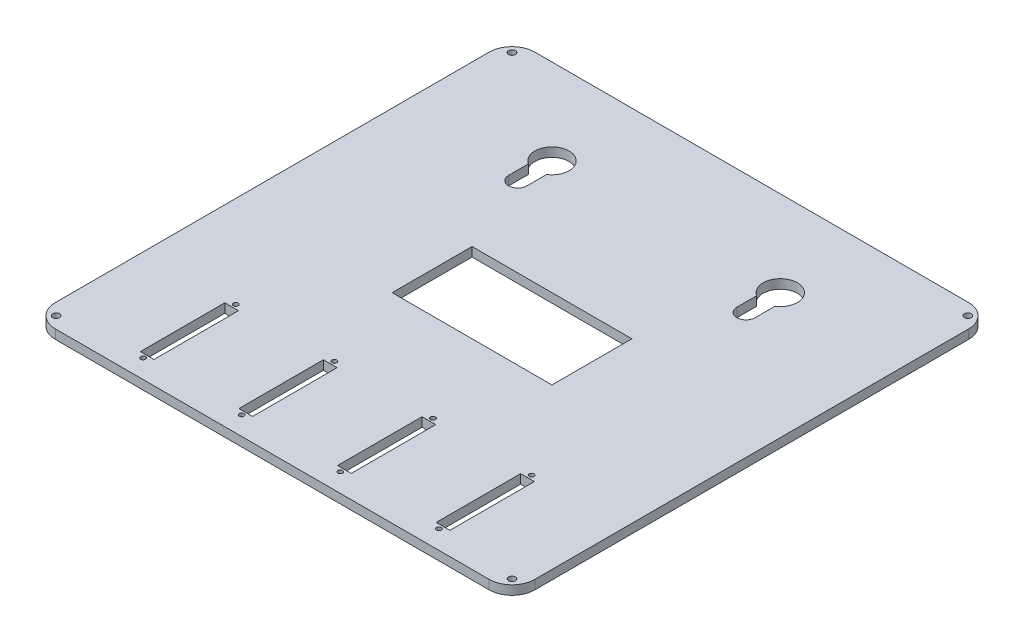
SolidWorks part; units mm, degrees
ref_plane "Front Plane" through (0, 0, 0) normal (0, 0, 1) x (1, 0, 0)
ref_plane "Top Plane" through (0, 0, 0) normal (0, 1, 0) x (1, 0, 0)
ref_plane "Right Plane" through (0, 0, 0) normal (1, 0, 0) x (0, 0, -1)
sketch "Sketch1" plane through (0, 0, 0) normal (0, 1, 0) x (1, 0, 0)
  line L0 (-101, -101) -> (-101, 101)
  line L5 (-105, -105) -> (105, -105)
  line L6 (-105, -105) -> (-105, 105)
  line L7 (-105, 105) -> (105, 105)
  line L8 (105, -105) -> (105, 105)
  line L9 (-101, 101) -> (101, 101)
  line L10 (101, -101) -> (101, 101)
  line L11 (-101, -101) -> (101, -101)
  line L12 (-101, 101) -> (-99.8333, 99.8333) construction
  line L13 (-55, 0) -> (55, 0) construction
  line L14 (-101, -101) -> (-99.8333, -99.8333) construction
  line L15 (0, -55) -> (0, 55) construction
  line L16 (101, -101) -> (99.8333, -99.8333) construction
  line L17 (101, 101) -> (99.8333, 99.8333) construction
  circle A1 centre (-99.8333, 99.8333) radius 1.5
  circle A2 centre (-99.8333, -99.8333) radius 1.5
  circle A3 centre (99.8333, -99.8333) radius 1.5
  circle A4 centre (99.8333, 99.8333) radius 1.5
  point P0 (0, 0)
  point P6 (-105, 0)
  point P7 (0, 105)
  dimension "D3" = 4
  dimension "D4" = 3
  dimension "D1" = 210
  dimension "D2" = 210
  dimension "D5" = 1.65
  dimension "D6" = 45
extrude "MainExtrude" add sketch "Sketch1" along normal mid plane 4 contours L6 L5 L8 L7
extrude "ScrewHoles" cut sketch "Sketch1<6>" along normal mid plane 4 contours A1 | A2 | A3 | A4
sketch "Sketch1<6>" plane through (0, 0, 0) normal (0, 1, 0) x (1, 0, 0) same geometry as "Sketch1"
fillet "RoundedCorners" radius 10 4 edges at (-105, 0, -105) (-105, 0, 105) (105, 0, -105) (105, 0, 105)
sketch "Sketch2" plane through (0, 2, 0) normal (0, 1, 0) x (1, 0, 0)
  line L0 (-50, 67.5) -> (-50, 52.5) construction
  line L1 (-67.8, -58) -> (-61.8, -58)
  line L2 (-67.8, -58) -> (-67.8, -95)
  line L3 (-67.8, -95) -> (-61.8, -95)
  line L4 (-61.8, -58) -> (-61.8, -95)
  line L5 (-24.6, -58) -> (-18.6, -58)
  line L6 (-24.6, -58) -> (-24.6, -95)
  line L7 (-24.6, -95) -> (-18.6, -95)
  line L8 (-18.6, -58) -> (-18.6, -95)
  line L9 (18.6, -58) -> (24.6, -58)
  line L10 (18.6, -58) -> (18.6, -95)
  line L11 (18.6, -95) -> (24.6, -95)
  line L12 (24.6, -58) -> (24.6, -95)
  line L13 (61.8, -58) -> (67.8, -58)
  line L14 (61.8, -58) -> (61.8, -95)
  line L15 (61.8, -95) -> (67.8, -95)
  line L16 (67.8, -58) -> (67.8, -95)
  line L17 (-95, -105) -> (95, -105) construction
  line L19 (-67.8, -58) -> (-105, -58) construction
  line L20 (-105, -95) -> (-105, 95) construction
  line L21 (-61.8, -58) -> (-24.6, -58) construction
  line L22 (-18.6, -58) -> (18.6, -58) construction
  line L23 (24.6, -58) -> (61.8, -58) construction
  line L25 (-105, 60) -> (-50, 60) construction
  line L26 (-95, 105) -> (95, 105) construction
  line L30 (-54, 52.5) -> (-54, 61.1557)
  line L31 (-46, 52.5) -> (-46, 61.1557)
  line L32 (0, -3.3) -> (0, 3.3) construction
  line L33 (46, 52.5) -> (46, 61.1557)
  line L34 (54, 52.5) -> (54, 61.1557)
  line L36 (35, -17.5) -> (-35, -17.5)
  line L37 (35, -17.5) -> (35, 17.5)
  line L38 (35, 17.5) -> (-35, 17.5)
  line L39 (-35, -17.5) -> (-35, 17.5)
  arc A0 (-54, 52.5) -> (-46, 52.5) centre (-50, 52.5) ccw
  arc A4 (-46, 61.1557) -> (-54, 61.1557) centre (-50, 67.5) ccw
  arc A5 (54, 52.5) -> (46, 52.5) centre (50, 52.5) cw
  arc A6 (46, 61.1557) -> (54, 61.1557) centre (50, 67.5) cw
  circle A7 centre (-64.8, -96.8) radius 1.05
  circle A8 centre (-64.8, -56.2) radius 1.05
  circle A9 centre (-21.6, -56.2) radius 1.05
  circle A10 centre (-21.6, -96.8) radius 1.05
  circle A11 centre (21.6, -56.2) radius 1.05
  circle A12 centre (21.6, -96.8) radius 1.05
  circle A13 centre (64.8, -56.2) radius 1.05
  circle A14 centre (64.8, -96.8) radius 1.05
  point P30 (0, 17.5)
  point P40 (-50, 60)
  point P42 (0, 0)
  point P48 (-35, 0)
  point P54 (-64.8, -95)
  point P58 (-61.8, -76.5)
  point P59 (-64.8, -58)
  point P60 (-21.6, -58)
  point P71 (-21.6, -95)
  dimension "D7" = 15
  dimension "D8" = 4
  dimension "D16" = 2.1
  dimension "D17" = 43.2
  dimension "D18" = 4
  dimension "D1" = 6
  dimension "D2" = 37
  dimension "D3" = 37.2
  dimension "D4" = 10
  dimension "D5" = 55
  dimension "D6" = 45
  dimension "D9" = 15
  dimension "D10" = 70
  dimension "D11" = 35
  dimension "D12" = 50
  dimension "D13" = 52.5
  dimension "D14" = 40.6
  dimension "D15" = 20.3
extrude "Knotches/Sliders" cut sketch "Sketch2" against normal up to surface (4 mm away) up to face at (-99.8333, -2, 98.3333)
sketch "Sketch6" plane through (71.6843, -2, 14.4809) normal (0, -1, 0) x (1, 0, 0)
  line L0 (-22.5243, 23.5191) -> (13.3157, 23.5191) construction
  line L1 (33.3157, 80.5191) -> (33.3157, -109.4809) construction
  line L2 (-9.8843, 43.5191) -> (-3.8843, 43.5191) construction
  circle A0 centre (-22.5243, 23.5191) radius 0.98
  circle A1 centre (-22.5243, 23.5191) radius 2
  circle A2 centre (13.3157, 23.5191) radius 2
  circle A3 centre (13.3157, 23.5191) radius 0.98
  circle A4 centre (-22.5243, -50.7509) radius 2
  circle A5 centre (-22.5243, -50.7509) radius 0.98
  circle A6 centre (13.3157, -50.7509) radius 0.98
  circle A7 centre (13.3157, -50.7509) radius 2
  dimension "D1" = 1.96
  dimension "D2" = 4
  dimension "D4" = 74.27
  dimension "D5" = 35.84
  dimension "D6" = 20
  dimension "D7" = 20
  dimension "D3" = 2
extrude "PCBHoles" add sketch "Sketch6" along normal blind 4
fillet "PCBRounds" radius 2 4 edges at (85, -2, -34.27) (49.16, -2, -34.27) (85, -2, 40) (49.16, -2, 40)
